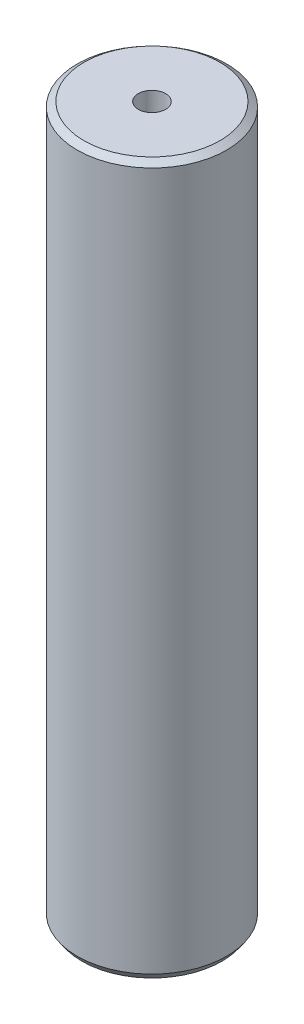
SolidWorks part; units mm, degrees
ref_plane "Front Plane" through (0, 0, 0) normal (0, 0, 1) x (1, 0, 0)
ref_plane "Top Plane" through (0, 0, 0) normal (0, 1, 0) x (1, 0, 0)
ref_plane "Right Plane" through (0, 0, 0) normal (1, 0, 0) x (0, 0, -1)
sketch "Sketch1" plane through (0, 0, 0) normal (0, 1, 0) x (1, 0, 0)
  circle A0 centre (0, 0) radius 5
  dimension "SHAFT_OD" = 10
extrude "Boss-Extrude1" add sketch "Sketch1" along normal blind 47.4859
sketch "Sketch2" plane through (0, 0, 0) normal (0, 1, 0) x (1, 0, 0)
  circle A0 centre (0, 0) radius 0.9145
  dimension "BORE_D" = 1.829
extrude "Cut-Extrude1" cut sketch "Sketch2" along normal through all
chamfer "Chamfer1" distance 0.3206 angle 54.702 2 edges at (0, 47.4859, 5) (0, 0, 5) first distance on face at (0, 47.4859, 5) first distance on face at (0, 0, 0.9145)
